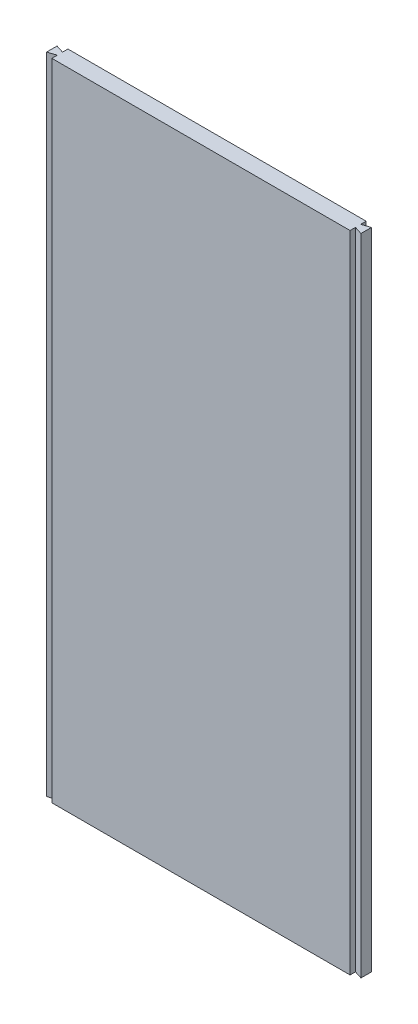
SolidWorks part; units mm, degrees
ref_plane "Front Plane" through (0, 0, 0) normal (0, 0, 1) x (1, 0, 0)
ref_plane "Top Plane" through (0, 0, 0) normal (0, 1, 0) x (1, 0, 0)
ref_plane "Right Plane" through (0, 0, 0) normal (1, 0, 0) x (0, 0, -1)
sketch "Sketch1" plane through (0, 0, 0) normal (0, 0, 1) x (1, 0, 0)
  line L1 (0, 0) -> (37, 0)
  line L2 (0, 0) -> (0, 80)
  line L3 (0, 80) -> (37, 80)
  line L4 (37, 0) -> (37, 80)
  dimension "D1" = 80
  dimension "D2" = 37
extrude "Boss-Extrude1" add sketch "Sketch1" along normal blind 2
sketch "Sketch2" plane through (0, 80, 0) normal (0, 1, 0) x (1, 0, 0)
  line L0 (37, -1) -> (38, -1) construction
  line L1 (37, -2) -> (37, 0) construction
  line L2 (38, -1.65) -> (38, -0.35)
  line L3 (37, -1) -> (37, -0.35) construction
  line L4 (37, -0.675) -> (38, -0.35)
  line L5 (37, -1) -> (37, -1.65) construction
  line L6 (37, -1.325) -> (38, -1.65)
  line L7 (37, -0.675) -> (37, -1)
  line L8 (37, -0.675) -> (37, -1.325)
  line L9 (18.5, 0) -> (18.5, -2) construction
  line L10 (37, 0) -> (0, 0) construction
  line L11 (37, -2) -> (0, -2) construction
  line L12 (0, -0.675) -> (-1, -0.35)
  line L13 (-1, -1.65) -> (-1, -0.35)
  line L14 (0, -1.325) -> (-1, -1.65)
  line L15 (0, -0.675) -> (0, -1.325)
  line M5 (37, -2) -> (37, 0)
  dimension "D1" = 1
  dimension "D2" = 0.65
extrude "Boss-Extrude2" add sketch "Sketch2" against normal up to surface (80 mm away) contours L6 L2 L4 M5 | L14 L13 L12 L15 region at (37.5556, 80, 1) up to face at (18.5, 0, 1)
